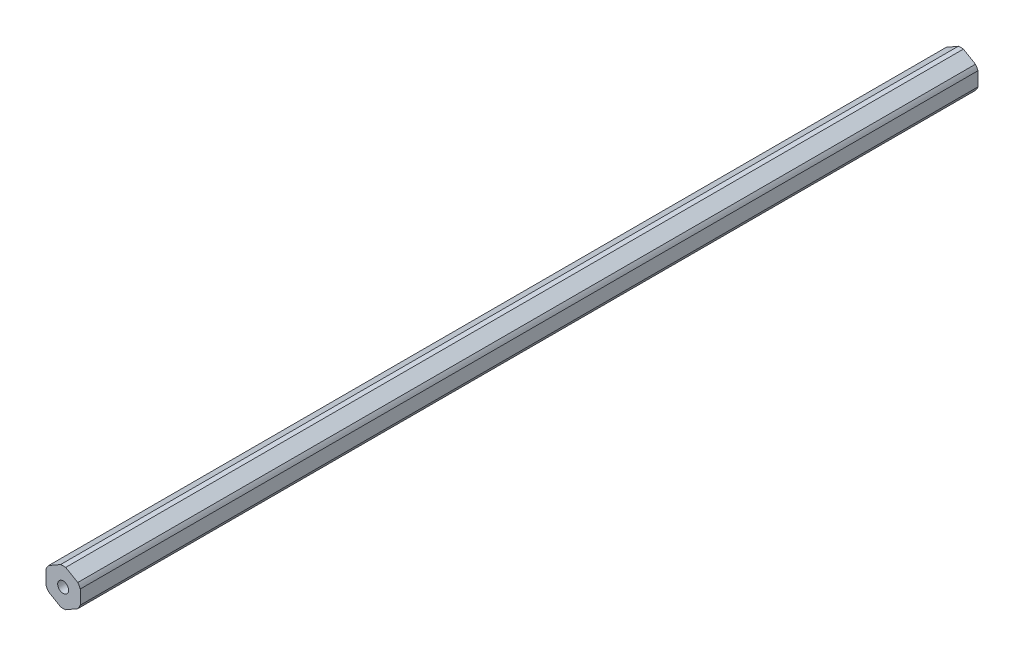
SolidWorks part; units mm, degrees
material "7075-T6 (SN)"
ref_plane "Front Plane" through (0, 0, 0) normal (0, 0, 1) x (1, 0, 0)
ref_plane "Top Plane" through (0, 0, 0) normal (0, 1, 0) x (1, 0, 0)
ref_plane "Right Plane" through (0, 0, 0) normal (1, 0, 0) x (0, 0, -1)
sketch "Sketch1" plane through (0, 0, 0) normal (0, 0, 1) x (1, 0, 0)
  line L1 (0, 7.3323) -> (-6.35, 3.6662)
  line L2 (-6.35, 3.6662) -> (-6.35, -3.6662)
  line L3 (-6.35, -3.6662) -> (0, -7.3323)
  line L4 (0, -7.3323) -> (6.35, -3.6662)
  line L5 (6.35, -3.6662) -> (6.35, 3.6662)
  line L6 (6.35, 3.6662) -> (0, 7.3323)
  circle A0 centre (0, 0) radius 6.35 construction
  circle A1 centre (0, 0) radius 6.858
  dimension "D1" = 12.7
  dimension "D2" = 13.716
extrude "Boss-Extrude1" add sketch "Sketch1" along normal mid plane 332.359 contours L5 A1 L6 L1 L2 L3 L4 region at (0, 0, 0)
sketch "Sketch2" plane through (0, 0, 166.1795) normal (0, 0, 1) x (1, 0, 0)
  circle A0 centre (0, 0) radius 2.0193
  dimension "D1" = 4.0386
extrude "Cut-Extrude1" cut sketch "Sketch2" against normal through all
